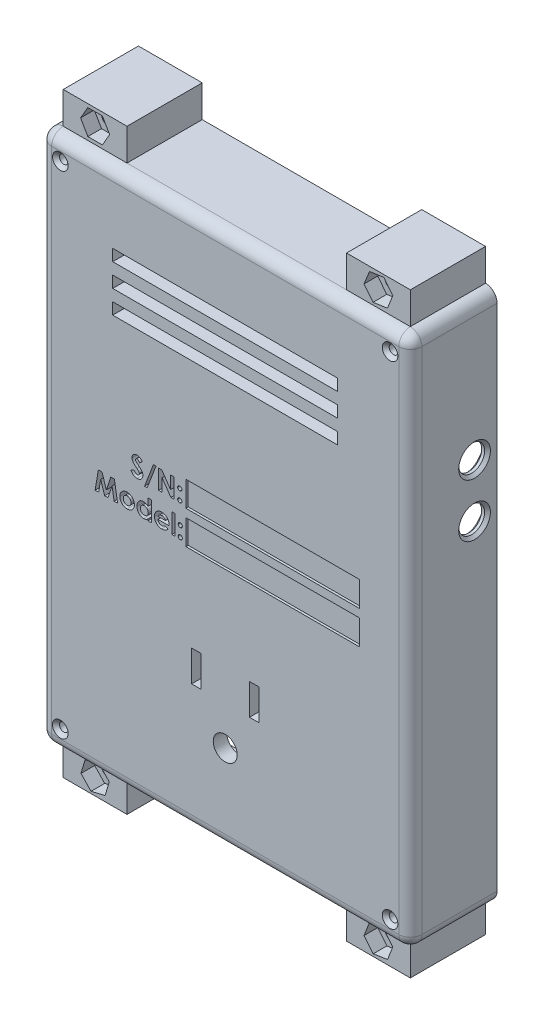
SolidWorks part; units mm, degrees
ref_plane "Front Plane" through (0, 0, 0) normal (0, 0, 1) x (1, 0, 0)
ref_plane "Top Plane" through (0, 0, 0) normal (0, 1, 0) x (1, 0, 0)
ref_plane "Right Plane" through (0, 0, 0) normal (1, 0, 0) x (0, 0, -1)
sketch "Sketch4" plane through (0, 0, 0) normal (0, 0, 1) x (1, 0, 0)
  line L1 (-36.195, 56.515) -> (36.195, 56.515)
  line L2 (-38.735, 53.975) -> (-38.735, -53.975)
  line L3 (-36.195, -56.515) -> (36.195, -56.515)
  line L4 (38.735, 53.975) -> (38.735, -53.975)
  arc A0 (-38.735, 53.975) -> (-36.195, 56.515) centre (-36.195, 53.975) ccw
  arc A1 (36.195, 56.515) -> (38.735, 53.975) centre (36.195, 53.975) ccw
  arc A2 (-36.195, -56.515) -> (-38.735, -53.975) centre (-36.195, -53.975) ccw
  arc A3 (38.735, -53.975) -> (36.195, -56.515) centre (36.195, -53.975) ccw
  dimension "D1" = 5.08
sketch "Sketch5" plane through (0, 0, 0) normal (0, 0, 1) x (1, 0, 0)
  line L0 (-40.64, -58.42) -> (40.64, -58.42)
  line L1 (-40.64, 58.42) -> (40.64, 58.42)
  line L2 (-40.64, 58.42) -> (-40.64, -58.42)
  line L3 (-40.64, -58.42) -> (40.64, -58.42) construction
  line L4 (40.64, 58.42) -> (40.64, -58.42)
  line L5 (-40.64, 58.42) -> (40.64, -58.42) construction
  line L6 (-40.64, -58.42) -> (40.64, 58.42) construction
  line L7 (-40.64, 58.42) -> (40.64, 58.42) construction
  line L9 (-40.64, 0) -> (40.64, 0) construction
  point P0 (0, 0)
sketch "Sketch8" plane through (0, 0, 0) normal (0, 0, 1) x (1, 0, 0)
  circle A0 centre (-36.195, 53.975) radius 0.9525
  circle A1 centre (-36.195, -53.975) radius 0.9525
  circle A2 centre (36.195, 53.975) radius 0.9525
  circle A3 centre (36.195, -53.975) radius 0.9525
  dimension "D1" = 1.905
extrude "Case" add sketch "Sketch5" along normal blind 12.7
extrude "Case Cut" cut sketch "Sketch4" along normal blind 9.7
ref_plane "Inside Back Plane" through (0, 0, 9.7) normal (0, 0, -1) x (-1, 0, 0)
sketch "Sketch11" plane through (0, 0, 9.7) normal (0, 0, -1) x (-1, 0, 0)
  circle A0 centre (-35.56, 48.641) radius 0.8255
  circle A1 centre (35.56, 48.641) radius 0.8255
  circle A2 centre (35.56, -48.641) radius 0.8255
  circle A3 centre (-35.56, -48.641) radius 0.8255
  dimension "D1" = 1.651
sketch "Sketch13" plane through (0, 0, 9.7) normal (0, 0, -1) x (-1, 0, 0)
  line L0 (-36.195, 51.435) -> (36.195, 51.435) construction
  line L1 (-36.195, -51.435) -> (36.195, -51.435) construction
  circle A0 centre (-35.56, 48.641) radius 2.159
  circle A1 centre (35.56, 48.641) radius 2.159
  circle A2 centre (-35.56, -48.641) radius 2.159
  circle A3 centre (35.56, -48.641) radius 2.159
  dimension "D1" = 4.318
  dimension "D2" = 2.794
  dimension "D5" = 2.794
extrude "Board Mount" add sketch "Sketch13" along normal blind 0.0001
extrude "Board Mount Screw Cut" cut sketch "Sketch11" along normal blind 5.588
extrude "FacePlate Screw Cut" cut sketch "Sketch8" along normal through all
sketch "Sketch14" plane through (0, 0, 9.7) normal (0, 0, -1) x (-1, 0, 0)
  line L0 (7.366, -27.559) -> (38.735, -27.559) construction
  line L1 (-7.366, -24.1554) -> (-5.334, -24.1554)
  line L2 (-7.366, -24.1554) -> (-7.366, -30.9626)
  line L3 (-7.366, -30.9626) -> (-5.334, -30.9626)
  line L4 (-5.334, -24.1554) -> (-5.334, -30.9626)
  line L5 (5.334, -24.1554) -> (7.366, -24.1554)
  line L6 (5.334, -24.1554) -> (5.334, -30.9626)
  line L7 (5.334, -30.9626) -> (7.366, -30.9626)
  line L8 (7.366, -24.1554) -> (7.366, -30.9626)
  line L10 (-7.366, -27.559) -> (-38.735, -27.559) construction
  line L13 (-36.195, -51.435) -> (36.195, -51.435) construction
  line L14 (-6.35, -24.1554) -> (-6.35, -30.9626) construction
  line L15 (6.35, -24.1554) -> (6.35, -30.9626) construction
  circle A0 centre (0, -39.497) radius 2.6289
  dimension "D4" = 5.2578
  dimension "D6" = 11.938
  dimension "D1" = 2.032
  dimension "D2" = 6.8072
  dimension "D3" = 12.7
  dimension "D5" = 11.938
ref_plane "Left Side Plane" through (40.64, 0, 0) normal (1, 0, 0) x (0, 0, -1)
sketch "Sketch18" plane through (40.64, 0, 0) normal (1, 0, 0) x (0, 0, -1)
  line L0 (-9.7, -53.975) -> (-9.7, 53.975) construction
  line L1 (-9.7, 51.435) -> (0, 51.435) construction
  line L3 (1.4, 28.575) -> (1.4, 11.7324) construction
  circle A1 centre (1.4, 28.575) radius 2.844
  circle A2 centre (1.4, 16.891) radius 2.844
  dimension "D2" = 5.688
  dimension "D1" = 22.86
  dimension "D3" = 11.1
  dimension "D4" = 11.684
extrude "Outlet Cut" cut sketch "Sketch14" against normal through all
ref_plane "Top Back Plane" through (0, 0, 0) normal (0, 0, -1) x (-1, 0, 0)
sketch "Sketch24" plane through (0, 0, 0) normal (0, 0, 1) x (1, 0, 0)
  line L0 (-40.64, -58.42) -> (40.64, -58.42)
  line L1 (-40.64, 58.42) -> (40.64, 58.42)
  line L2 (-40.64, 58.42) -> (-40.64, -58.42)
  line L3 (-40.64, -58.42) -> (40.64, -58.42) construction
  line L4 (40.64, 58.42) -> (40.64, -58.42)
  line L5 (-40.64, 58.42) -> (40.64, -58.42) construction
  line L6 (-40.64, -58.42) -> (40.64, 58.42) construction
  line L7 (-40.64, 58.42) -> (40.64, 58.42) construction
  line L9 (-40.64, 0) -> (40.64, 0) construction
  point P0 (0, 0)
extrude "Boss-Extrude1" add sketch "Sketch24" against normal blind 6.35
sketch "Sketch26" plane through (0, 0, 0) normal (0, 0, 1) x (1, 0, 0)
  line L1 (-36.195, 56.515) -> (36.195, 56.515)
  line L2 (-38.735, 53.975) -> (-38.735, -53.975)
  line L3 (-36.195, -56.515) -> (36.195, -56.515)
  line L4 (38.735, 53.975) -> (38.735, -53.975)
  arc A0 (-38.735, 53.975) -> (-36.195, 56.515) centre (-36.195, 53.975) ccw
  arc A1 (36.195, 56.515) -> (38.735, 53.975) centre (36.195, 53.975) ccw
  arc A2 (-36.195, -56.515) -> (-38.735, -53.975) centre (-36.195, -53.975) ccw
  arc A3 (38.735, -53.975) -> (36.195, -56.515) centre (36.195, -53.975) ccw
  dimension "D1" = 5.08
extrude "Cut-Extrude1" cut sketch "Sketch26" against normal blind 6.35
fillet "Fillet11" radius 2.54 1 edges at (40.64, -58.42, 3.175) type face fillet first side face at (40.64, 0, 3.175) second side face at (0, -58.42, 3.175)
fillet "Fillet12" radius 2.54 1 edges at (40.64, 58.42, 3.175) type face fillet first side face at (0, 58.42, 3.175) second side face at (40.64, 1.27, 3.175)
fillet "Fillet13" radius 2.54 1 edges at (-40.64, 58.42, 3.175) type face fillet first side face at (-1.27, 58.42, 3.175) second side face at (-40.64, 0, 3.175)
sketch "Sketch28" plane through (0, 0, 0) normal (0, 0, -1) x (-1, 0, 0)
  circle A0 centre (-36.195, 53.975) radius 0.9525
  circle A1 centre (-36.195, -53.975) radius 0.9525
  circle A2 centre (36.195, 53.975) radius 0.9525
  circle A3 centre (36.195, -53.975) radius 0.9525
  dimension "D1" = 1.905
extrude "Cut-Extrude3" cut sketch "Sketch28" along normal through all
fillet "Fillet14" radius 2.54 1 edges at (-40.64, -58.42, 3.175) type face fillet first side face at (-40.64, -1.27, 3.175) second side face at (-1.27, -58.42, 3.175)
ref_plane "Plane1" through (0, 0, -6.35) normal (0, 0, -1) x (-1, 0, 0)
sketch "Sketch30" plane through (0, 0, -6.35) normal (0, 0, -1) x (-1, 0, 0)
  line L8 (-39.624, -57.404) -> (39.624, -57.404)
  line L10 (39.624, 57.404) -> (39.624, -57.404)
  line L11 (-39.624, 57.404) -> (39.624, 57.404)
  line L12 (-39.624, 57.404) -> (-39.624, -57.404)
  point P0 (0, 0)
extrude "Cut-Extrude4" cut sketch "Sketch30" against normal blind 2.032
fillet "Fillet15" radius 2.54 1 edges at (39.624, 57.404, -5.334) type face fillet first side face at (39.624, 0, -5.334) second side face at (0, 57.404, -5.334)
fillet "Fillet16" radius 2.54 1 edges at (-39.624, 57.404, -5.334) type face fillet first side face at (-39.624, 0, -5.334) second side face at (-1.27, 57.404, -5.334)
fillet "Fillet17" radius 2.54 1 edges at (-39.624, -57.404, -5.334) type face fillet first side face at (-39.624, -1.27, -5.334) second side face at (0, -57.404, -5.334)
fillet "Fillet18" radius 2.54 1 edges at (39.624, -57.404, -5.334) type face fillet first side face at (39.624, -1.27, -5.334) second side face at (1.27, -57.404, -5.334)
ref_plane "Plane2" through (0, 0, 12.7) normal (0, 0, 1) x (1, 0, 0)
extrude "Cut-Extrude5" cut sketch "Sketch18" against normal blind 2.54
chamfer "Chamfer6" distance 0.635 angle 45 4 edges at (40.64, 16.891, -4.244) (40.64, 28.575, -4.244) (38.735, 25.731, -1.4) (38.735, 14.047, -1.4)
fillet "Fillet19" radius 2.54 8 edges at (39.8961, -57.6761, 12.7) (0, -58.42, 12.7) (-39.8961, -57.6761, 12.7) (-40.64, 0, 12.7) (-39.8961, 57.6761, 12.7) (0, 58.42, 12.7) (39.8961, 57.6761, 12.7) (40.64, 0, 12.7)
chamfer "Chamfer7" distance 0.762 angle 45 4 edges at (37.1475, 53.975, 12.7) (-35.2425, 53.975, 12.7) (-35.2425, -53.975, 12.7) (37.1475, -53.975, 12.7)
sketch "Sketch31" plane through (0, 0, 12.7) normal (0, 0, 1) x (1, 0, 0)
  line L1 (-8.6427, 7.3091) -> (29.4287, 7.3091)
  line L2 (-8.6427, 7.3091) -> (-8.6427, 1.7965)
  line L3 (-8.6427, 1.7965) -> (29.4287, 1.7965)
  line L4 (29.4287, 7.3091) -> (29.4287, 1.7965)
  line L5 (-8.6427, 0) -> (29.4287, 0)
  line L6 (-8.6427, 0) -> (-8.6427, -5.5047)
  line L7 (-8.6427, -5.5047) -> (29.4287, -5.5047)
  line L8 (29.4287, 0) -> (29.4287, -5.5047)
extrude "Cut-Extrude6" cut sketch "Sketch31" against normal blind 0.508
sketch "Sketch32" plane through (0, 0, 12.7) normal (0, 0, 1) x (1, 0, 0)
  text T0 "S/N:" font "Century Gothic" height in points 16
  text T1 "Model:" font "Century Gothic" height in points 16
extrude "Cut-Extrude7" cut sketch "Sketch32" against normal blind 1.905
sketch "Sketch33" plane through (0, 0, 12.7) normal (0, 0, 1) x (1, 0, 0)
  line L0 (-24.6942, 41.91) -> (-38.1, 41.91) construction
  line L1 (-24.6942, 43.18) -> (24.6942, 43.18)
  line L2 (-24.6942, 43.18) -> (-24.6942, 40.64)
  line L3 (-24.6942, 40.64) -> (24.6942, 40.64)
  line L4 (24.6942, 43.18) -> (24.6942, 40.64)
  line L5 (-38.1, 55.88) -> (-38.1, -55.88) construction
  line L6 (24.6942, 41.91) -> (38.1, 41.91) construction
  line L7 (38.1, -55.88) -> (38.1, 55.88) construction
  line L8 (0, 40.64) -> (0, 38.1) construction
  line L9 (-24.6942, 38.1) -> (24.6942, 38.1)
  line L10 (-24.6942, 38.1) -> (-24.6942, 35.56)
  line L11 (-24.6942, 35.56) -> (24.6942, 35.56)
  line L12 (24.6942, 38.1) -> (24.6942, 35.56)
  line L13 (0, 35.56) -> (0, 33.02) construction
  line L14 (-24.6942, 33.02) -> (24.6942, 33.02)
  line L15 (-24.6942, 33.02) -> (-24.6942, 30.48)
  line L16 (-24.6942, 30.48) -> (24.6942, 30.48)
  line L17 (24.6942, 33.02) -> (24.6942, 30.48)
  line L18 (0, 43.18) -> (0, 55.88) construction
  line L19 (38.1, 55.88) -> (-38.1, 55.88) construction
  dimension "D1" = 2.54
  dimension "D2" = 2.54
  dimension "D3" = 2.54
  dimension "D4" = 12.7
extrude "Cut-Extrude8" cut sketch "Sketch33" against normal blind 27.94
sketch "Sketch34" plane through (0, 58.42, 0) normal (0, 1, 0) x (1, 0, 0)
  line L0 (-38.1, -10.16) -> (38.1, -10.16) construction
  line L1 (-38.1, 6.35) -> (-24.1, 6.35)
  line L2 (-38.1, 6.35) -> (-38.1, -10.16)
  line L3 (-38.1, -10.16) -> (-24.1, -10.16)
  line L4 (-24.1, 6.35) -> (-24.1, -10.16)
  line L6 (38.1, 6.35) -> (24.1, 6.35)
  line L7 (38.1, 6.35) -> (38.1, -10.16)
  line L8 (38.1, -10.16) -> (24.1, -10.16)
  line L9 (24.1, 6.35) -> (24.1, -10.16)
  dimension "D1" = 14
extrude "Boss-Extrude2" add sketch "Sketch34" along normal blind 7
sketch "Sketch35" plane through (0, -58.42, 0) normal (0, -1, 0) x (1, 0, 0)
  line L0 (38.1, 10.16) -> (-38.1, 10.16) construction
  line L1 (-38.1, -6.35) -> (-24.1, -6.35)
  line L2 (-38.1, -6.35) -> (-38.1, 10.16)
  line L3 (-38.1, 10.16) -> (-24.1, 10.16)
  line L4 (-24.1, -6.35) -> (-24.1, 10.16)
  line L5 (-38.1, -6.35) -> (38.1, -6.35) construction
  line L6 (38.1, 10.16) -> (24.1, 10.16)
  line L7 (38.1, 10.16) -> (38.1, -6.35)
  line L8 (38.1, -6.35) -> (24.1, -6.35)
  line L9 (24.1, 10.16) -> (24.1, -6.35)
  dimension "D1" = 14
extrude "Boss-Extrude3" add sketch "Sketch35" along normal blind 7
sketch "Sketch36" plane through (0, 0, 10.16) normal (0, 0, 1) x (1, 0, 0)
  circle A0 centre (-31.1, -61.92) radius 1.575
  circle A1 centre (31.1, -61.92) radius 1.575
  circle A2 centre (31.1, 61.92) radius 1.575
  circle A3 centre (-31.1, 61.92) radius 1.575
  dimension "D1" = 3.15
extrude "Cut-Extrude9" cut sketch "Sketch36" along direction (0, 0, 1) on the side against the normal up to surface (16.51 mm away) up to face at (0, 0, -6.35)
sketch "Sketch38" plane through (0, 0, 10.16) normal (0, 0, 1) x (1, 0, 0)
  line L1 (-28.0015, -61.1743) -> (-30.1965, -58.8638)
  line L2 (-30.1965, -58.8638) -> (-33.295, -59.6094)
  line L3 (-33.295, -59.6094) -> (-34.1985, -62.6657)
  line L4 (-34.1985, -62.6657) -> (-32.0035, -64.9762)
  line L5 (-32.0035, -64.9762) -> (-28.905, -64.2306)
  line L6 (-28.905, -64.2306) -> (-28.0015, -61.1743)
  line L7 (34.2485, -61.4262) -> (32.2466, -58.9464)
  line L8 (32.2466, -58.9464) -> (29.0981, -59.4403)
  line L9 (29.0981, -59.4403) -> (27.9515, -62.4138)
  line L10 (27.9515, -62.4138) -> (29.9534, -64.8936)
  line L11 (29.9534, -64.8936) -> (33.1019, -64.3997)
  line L12 (33.1019, -64.3997) -> (34.2485, -61.4262)
  line L13 (34.2544, 62.3744) -> (32.2837, 64.879)
  line L14 (32.2837, 64.879) -> (29.1293, 64.4246)
  line L15 (29.1293, 64.4246) -> (27.9456, 61.4656)
  line L16 (27.9456, 61.4656) -> (29.9163, 58.961)
  line L17 (29.9163, 58.961) -> (33.0707, 59.4154)
  line L18 (33.0707, 59.4154) -> (34.2544, 62.3744)
  line L19 (-27.913, 61.92) -> (-29.5065, 64.68)
  line L20 (-29.5065, 64.68) -> (-32.6935, 64.68)
  line L21 (-32.6935, 64.68) -> (-34.287, 61.92)
  line L22 (-34.287, 61.92) -> (-32.6935, 59.16)
  line L23 (-32.6935, 59.16) -> (-29.5065, 59.16)
  line L24 (-29.5065, 59.16) -> (-27.913, 61.92)
  circle A0 centre (-31.1, -61.92) radius 2.76 construction
  circle A1 centre (31.1, -61.92) radius 2.76 construction
  circle A2 centre (31.1, 61.92) radius 2.76 construction
  circle A3 centre (-31.1, 61.92) radius 2.76 construction
  dimension "D1" = 5.52
extrude "Cut-Extrude10" cut sketch "Sketch38" against normal blind 3
